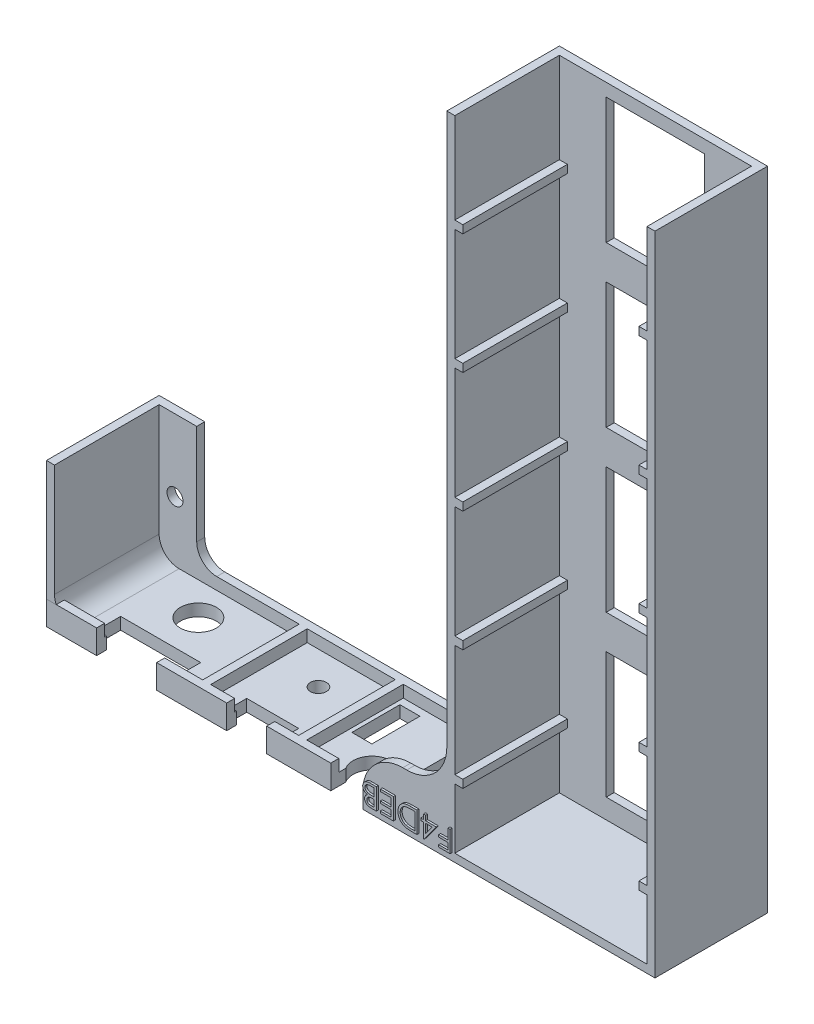
SolidWorks part; units mm, degrees
ref_plane "Front Plane" through (0, 0, 0) normal (0, 0, 1) x (1, 0, 0)
ref_plane "Top Plane" through (0, 0, 0) normal (0, 1, 0) x (1, 0, 0)
ref_plane "Right Plane" through (0, 0, 0) normal (1, 0, 0) x (0, 0, -1)
sketch "Esquisse1" plane through (0, 0, 0) normal (0, 1, 0) x (1, 0, 0)
  line L1 (-50, 14.0602) -> (50, 14.0602)
  line L2 (-50, 14.0602) -> (-50, -14.0602)
  line L3 (-50, -14.0602) -> (50, -14.0602)
  line L4 (50, 14.0602) -> (50, -14.0602)
  line L5 (-50, 14.0602) -> (50, -14.0602) construction
  line L6 (-50, -14.0602) -> (50, 14.0602) construction
  point P0 (0, 0)
extrude "Boss.-Extru.1" add sketch "Esquisse1" along normal blind 3
sketch "Esquisse2" plane through (0, 3, 0) normal (0, 1, 0) x (1, 0, 0)
  line L0 (-5, -14.0602) -> (-5, -11.5602)
  line L1 (-50, -14.0602) -> (50, -14.0602) construction
  line L2 (-5, -11.5602) -> (-6.5, -11.5602)
  line L3 (5, -11.5602) -> (5, -14.0602)
  line L4 (5, -14.0602) -> (-5, -14.0602)
  line L5 (-6.5, -11.5602) -> (-6.5, -7.5602)
  line L6 (-6.5, -7.5602) -> (6.5, -7.5602)
  line L7 (6.5, -7.5602) -> (6.5, -11.5602)
  line L8 (6.5, -11.5602) -> (5, -11.5602)
  line L9 (-37.5, -14.0602) -> (-37.5, -11.5602)
  line L10 (-37.5, -11.5602) -> (-40, -11.5602)
  line L11 (-40, -11.5602) -> (-40, -5.5602)
  line L12 (-40, -5.5602) -> (-20, -5.5602)
  line L13 (-20, -5.5602) -> (-20, -11.5602)
  line L14 (-20, -11.5602) -> (-22.5, -11.5602)
  line L15 (-22.5, -11.5602) -> (-22.5, -14.0602)
  line L16 (-22.5, -14.0602) -> (-37.5, -14.0602)
  line L17 (21, -14.0602) -> (29, -14.0602)
  line L18 (21, -14.0602) -> (21, -10.3131)
  line L19 (29, -14.0602) -> (29, -10.3131)
  line L20 (21, -10.3131) -> (29, -10.3131) construction
  line L21 (-50, 14.0602) -> (-50, -14.0602) construction
  line L22 (25, -10.3131) -> (25, -7.7513) construction
  line L24 (19, -1.7796) -> (31, -1.7796) construction
  line L25 (19, 10.2204) -> (14, 10.2204)
  line L26 (19, 10.2204) -> (19, -1.7796)
  line L27 (19, -1.7796) -> (14, -1.7796)
  line L28 (14, 10.2204) -> (14, -1.7796)
  line L29 (36, 10.2204) -> (31, 10.2204)
  line L30 (36, 10.2204) -> (36, -1.7796)
  line L31 (36, -1.7796) -> (31, -1.7796)
  line L32 (31, 10.2204) -> (31, -1.7796)
  arc A0 (21, -10.3131) -> (29, -10.3131) centre (25, -7.7513) cw
  circle A1 centre (-30, 3.8671) radius 4.5
  circle A2 centre (0, 3.8671) radius 2
  point P7 (0, -7.5602)
  point P11 (0, -14.0602)
  point P21 (-30, -5.5602)
  point P22 (-30, -14.0602)
  point P31 (25, -10.3131)
  point P33 (25, -14.0602)
  point P46 (25, -1.7796)
  line M19 (-50, -14.0602) -> (50, -14.0602)
  dimension "D8" = 20
  dimension "D12" = 5
  dimension "D1" = 10
  dimension "D2" = 13
  dimension "D3" = 4
  dimension "D4" = 2.5
  dimension "D5" = 15
  dimension "D6" = 20
  dimension "D7" = 6
  dimension "D9" = 8
  dimension "D10" = 30
  dimension "D11" = 25
  dimension "D13" = 12
  dimension "D14" = 12
extrude "Enlèv. mat.-Extru.7" cut sketch "Esquisse2" against normal through all contours A1 | L15 L14 L13 L12 L11 L10 L9 M19 | L8 L7 L6 L5 L2 L0 L3 M19 | A2 | L25 L28 L27 L26 | A0 L18 L19 M19 | L32 L31 L30 L29 region at (25, 3, 8.7714) region at (0, 3, 10.6154) region at (-30, 3, 9.5721) region at (16.5, 3, -4.2204) region at (-30, 3, -3.8671) region at (0, 3, -3.8671)
sketch "Esquisse3" plane through (0, 3, 0) normal (0, 1, 0) x (1, 0, 0)
  line L0 (-50, 14.0602) -> (50, 14.0602)
  line L1 (50, 14.0602) -> (-50, 14.0602) construction
  line L2 (50, -14.0602) -> (29, -14.0602)
  line L3 (29, -14.0602) -> (29, -12.0602)
  line L5 (29, -12.0602) -> (50, -12.0602)
  line L6 (29, -14.0602) -> (50, -14.0602) construction
  line L7 (-48, 12.0602) -> (-13, 12.0602)
  line L8 (-48, 12.0602) -> (-48, -12.0602)
  line L9 (-48, -12.0602) -> (-37.5, -12.0602)
  line L10 (-37.5, -14.0602) -> (-37.5, -11.5602) construction
  line L11 (-37.5, -12.0602) -> (-37.5, -14.0602)
  line L12 (-37.5, -14.0602) -> (-50, -14.0602)
  line L13 (-50, -14.0602) -> (-50, 14.0602)
  line L14 (-50, 14.0602) -> (-50, -14.0602) construction
  line L15 (-5, -14.0602) -> (-5, -11.5602) construction
  line L16 (-22.5, -14.0602) -> (-5, -14.0602)
  line L17 (-22.5, -14.0602) -> (-22.5, -12.0602)
  line L18 (-22.5, -12.0602) -> (-13, -12.0602)
  line L19 (-5, -14.0602) -> (-5, -12.0602)
  line L20 (21, -14.0602) -> (21, -10.3131) construction
  line L21 (5, -14.0602) -> (21, -14.0602)
  line L22 (5, -14.0602) -> (5, -12.0602)
  line L23 (5, -12.0602) -> (11, -12.0602)
  line L24 (21, -14.0602) -> (21, -12.0602)
  line L25 (13, -12.0602) -> (21, -12.0602)
  line L26 (-11, -12.0602) -> (-5, -12.0602)
  line L27 (-13, -12.0602) -> (-13, 12.0602)
  line L28 (-11, 12.0602) -> (11, 12.0602)
  line L29 (-11, -12.0602) -> (-11, 12.0602)
  line L30 (13, 12.0602) -> (50, 12.0602)
  line L31 (11, -12.0602) -> (11, 12.0602)
  line L32 (50, 14.0602) -> (50, 12.0602)
  line L33 (13, -12.0602) -> (13, 12.0602)
  line L34 (50, -12.0602) -> (50, -14.0602)
  dimension "D1" = 2
  dimension "D2" = 2
  dimension "D5" = 2
  dimension "D6" = 2
  dimension "D7" = 2
  dimension "D8" = 35
extrude "Boss.-Extru.2" add sketch "Esquisse3" along normal blind 3
sketch "Esquisse4" plane through (0, 6, 0) normal (0, 1, 0) x (1, 0, 0)
  line L0 (-48, 12.0602) -> (-48, -14.0831)
  line L1 (-48, -12.0602) -> (-48, 12.0602) construction
  line L2 (-48, -14.0831) -> (-50, -14.0831)
  line L3 (-50, 14.0602) -> (-50, -14.0602) construction
  line L4 (-50, -14.0831) -> (-50, 14.0602)
  line L5 (-50, 14.0602) -> (-38.6068, 14.0602)
  line L6 (50, 14.0602) -> (-50, 14.0602) construction
  line L7 (-38.6068, 14.0602) -> (-38.6068, 12.0602)
  line L8 (-48, 12.0602) -> (-13, 12.0602) construction
  line L9 (-38.6068, 12.0602) -> (-48, 12.0602)
extrude "Boss.-Extru.3" add sketch "Esquisse4" along normal blind 30
sketch "Esquisse5" plane through (0, 0, -14.0602) normal (0, 0, -1) x (-1, 0, 0)
  circle A0 centre (44.0299, 18.0605) radius 2
extrude "Enlèv. mat.-Extru.8" cut sketch "Esquisse5" against normal blind 10
fillet "Congé1" radius 5 2 edges at (-38.6068, 6, -13.0602) (-48, 3, 0)
sketch "Esquisse6" plane through (50, 0, 0) normal (1, 0, 0) x (0, 0, -1)
  line L1 (14.0602, 0) -> (-14.0602, 0)
  line L2 (14.0602, 0) -> (14.0602, 2)
  line L3 (14.0602, 2) -> (-14.0602, 2)
  line L4 (-14.0602, 0) -> (-14.0602, 2)
  dimension "D1" = 2
extrude "Boss.-Extru.4" add sketch "Esquisse6" along normal blind 52
sketch "Esquisse7" plane through (0, 2, 0) normal (0, 1, 0) x (1, 0, 0)
  line L0 (50, 14.0602) -> (50, -14.0602)
  line L1 (50, -14.0602) -> (52, -14.0602)
  line L2 (102, -14.0602) -> (50, -14.0602) construction
  line L3 (52, -14.0602) -> (52, 12.0602)
  line L4 (52, 12.0602) -> (100, 12.0602)
  line L5 (100, 12.0602) -> (100, -14.0602)
  line L6 (100, -14.0602) -> (102, -14.0602)
  line L7 (102, -14.0602) -> (102, 14.0602)
  line L8 (102, 14.0602) -> (102, -14.0602) construction
  line L9 (102, 14.0602) -> (50, 14.0602) construction
  line L10 (102, 14.0602) -> (50, 14.0602)
  dimension "D1" = 2
  dimension "D2" = 2
  dimension "D3" = 2
extrude "Boss.-Extru.5" add sketch "Esquisse7" along normal blind 159.6
sketch "Esquisse8" plane through (52, 0, 0) normal (1, 0, 0) x (0, 0, -1)
  line L0 (-14.0602, 161.6) -> (-14.0602, 2) construction
  line L1 (-14.0602, 19) -> (12.0602, 19)
  line L2 (-14.0602, 19) -> (-14.0602, 17)
  line L3 (-14.0602, 17) -> (12.0602, 17)
  line L4 (12.0602, 19) -> (12.0602, 17)
  line L5 (12.0602, 161.6) -> (12.0602, 2) construction
  line L6 (-14.0602, 2) -> (12.0602, 2) construction
  dimension "D2" = 2
  dimension "D3" = 15
extrude "Boss.-Extru.6" add sketch "Esquisse8" along normal blind 2
sketch "Esquisse9" plane through (0, 2, 0) normal (0, 1, 0) x (1, 0, 0)
  line L0 (76, -14.0602) -> (76, 12.0602) construction
  line L1 (100, -14.0602) -> (52, -14.0602) construction
  line L2 (52, 12.0602) -> (100, 12.0602) construction
ref_plane "Plan4" through (76, 0, 0) normal (1, 0, 0) x (0, 0, -1)
sketch "Esquisse10" plane through (0, 0, -12.0602) normal (0, 0, 1) x (1, 0, 0)
  line L0 (100, 161.6) -> (-44.0299, 161.6) construction
  line L1 (-44.0299, 161.6) -> (-44.0299, 18.0605) construction
pattern_linear "Répétition linéaire1" count 5 spacing 30 along (0, 1, 0) of "Boss.-Extru.6"
mirror "Symétrie2" about plane through (76, 0, 0) normal (1, 0, 0) of "Répétition linéaire1", "Boss.-Extru.6"
sketch "Esquisse11" plane through (0, 0, -12.0602) normal (0, 0, 1) x (1, 0, 0)
  line L0 (76, -14.3662) -> (76, 14.3662) construction
  line L1 (88.2954, 6.9254) -> (63.7046, 6.9254)
  line L2 (88.2954, 6.9254) -> (88.2954, 38.3929)
  line L3 (88.2954, 38.3929) -> (63.7046, 38.3929)
  line L4 (63.7046, 6.9254) -> (63.7046, 38.3929)
  line L5 (88.2954, 6.9254) -> (63.7046, 38.3929) construction
  line L6 (88.2954, 38.3929) -> (63.7046, 6.9254) construction
  point P0 (76, 22.6591)
extrude "Enlèv. mat.-Extru.9" cut sketch "Esquisse11" against normal through all
pattern_linear "Répétition linéaire2" count 4 spacing 40 along (0, 1, 0) of "Enlèv. mat.-Extru.9"
sketch "Esquisse13" plane through (0, 0, 0) normal (0, -1, 0) x (1, 0, 0)
  circle A0 centre (37.1336, 9.539) radius 2
  circle A1 centre (45.1652, 9.539) radius 0.6
extrude "Enlèv. mat.-Extru.10" cut sketch "Esquisse13" against normal blind 5
sketch "Esquisse14" plane through (0, 6, 0) normal (0, 1, 0) x (1, 0, 0)
  line L1 (29, -12.0602) -> (50, -12.0602)
  line L2 (29, -12.0602) -> (29, -14.0602)
  line L3 (29, -14.0602) -> (50, -14.0602)
  line L4 (50, -12.0602) -> (50, -14.0602)
extrude "Boss.-Extru.7" add sketch "Esquisse14" along normal blind 8
fillet "Congé2" radius 10 2 edges at (50, 14, 13.0602) (29, 14, 13.0602)
sketch "Esquisse15" plane through (0, 0, 14.0602) normal (0, 0, 1) x (1, 0, 0)
  line L0 (52, 7.0865) -> (29.6325, 7.0865) construction
  text T0 "F4DEB" font "Century Gothic" height in points 20
extrude "Boss.-Extru.8" add sketch "Esquisse15" along normal blind 0.5
